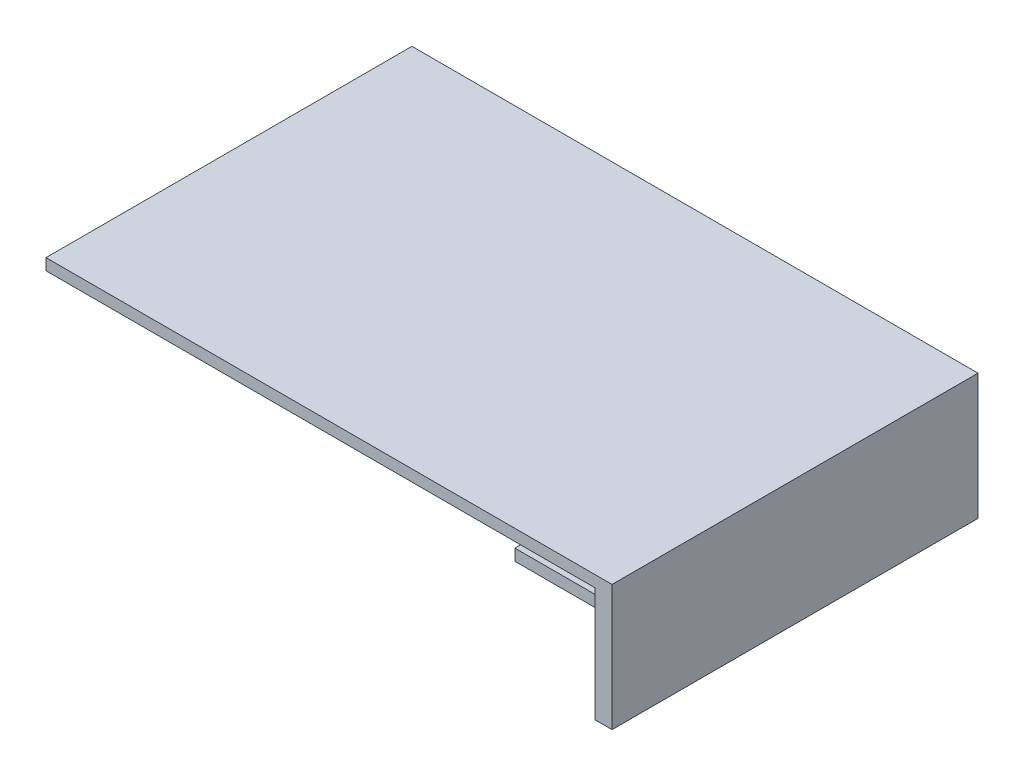
SolidWorks part; units mm, degrees
ref_plane "Front Plane" through (0, 0, 0) normal (0, 0, 1) x (1, 0, 0)
ref_plane "Top Plane" through (0, 0, 0) normal (0, 1, 0) x (1, 0, 0)
ref_plane "Right Plane" through (0, 0, 0) normal (1, 0, 0) x (0, 0, -1)
sketch "Sketch1" plane through (0, -30.7576, 0) normal (0, -1, 0) x (-1, 0, 0)
  line L0 (-80.663, 43.044) -> (-85.4255, 43.044)
  line L1 (-85.4255, 43.044) -> (-85.4255, -58.556)
  line L2 (-85.4255, -58.556) -> (-80.663, -58.556)
  line L3 (-80.663, -58.556) -> (-80.663, 43.044)
  dimension "D1" = 4.7625
extrude "Boss-Extrude1" add sketch "Sketch1" against normal offset from surface (34.925 mm away) 3.175 offset beyond the face yes
sketch "Sketch2" plane through (80.663, 0, 0) normal (-1, 0, 0) x (0, 0, 1)
  line L0 (58.556, 4.1674) -> (58.556, -30.7576) construction
  line L1 (-43.044, 4.1674) -> (58.556, 4.1674)
  line L2 (-43.044, 4.1674) -> (-43.044, 0.9924)
  line L3 (-43.044, 0.9924) -> (58.556, 0.9924)
  line L4 (58.556, 4.1674) -> (58.556, 0.9924)
  line L5 (-43.044, 0.9924) -> (58.556, 0.9924) construction
  line L6 (-43.044, 4.1674) -> (-43.044, -30.7576) construction
  line L8 (-39.869, -3.7701) -> (-39.869, -6.9451)
  line L10 (55.381, -3.7701) -> (55.381, -6.9451)
  line L15 (-39.869, -6.9451) -> (-38.2815, -6.9451)
  line L16 (-38.2815, -27.5826) -> (-38.2815, 0.9924) construction
  line L17 (-38.2815, -6.9451) -> (-38.2815, -3.7701)
  line L18 (-38.2815, -3.7701) -> (-39.869, -3.7701)
  line L19 (55.381, -6.9451) -> (53.7935, -6.9451)
  line L20 (53.7935, -27.5826) -> (53.7935, 0.9924) construction
  line L21 (53.7935, -6.9451) -> (53.7935, -3.7701)
  line L22 (53.7935, -3.7701) -> (55.381, -3.7701)
  dimension "D1" = 3.175
  dimension "D2" = 3.175
  dimension "D3" = 3.175
  dimension "D4" = 7.9375
extrude "Boss-Extrude2" add sketch "Sketch2" along normal up to surface (152.4 mm away) contours L3 L4 L1 L2
extrude "Boss-Extrude3" add sketch "Sketch2<4>" along normal blind 25.4 contours L19 L21 L22 L10 | L15 L17 L18 L8
sketch "Sketch2<4>" plane through (80.663, 0, 0) normal (-1, 0, 0) x (0, 0, 1) same geometry as "Sketch2"
